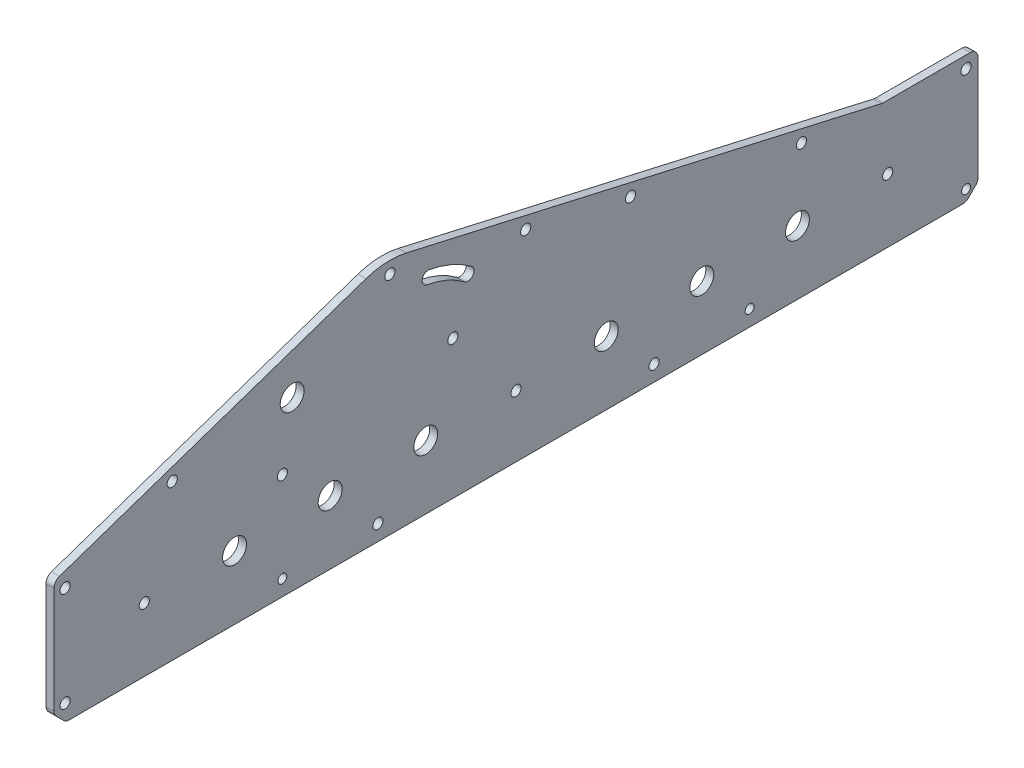
SolidWorks part; units mm, degrees
ref_plane "Front Plane" through (0, 0, 0) normal (0, 0, 1) x (1, 0, 0)
ref_plane "Top Plane" through (0, 0, 0) normal (0, 1, 0) x (1, 0, 0)
ref_plane "Right Plane" through (0, 0, 0) normal (1, 0, 0) x (0, 0, -1)
sketch "Sketch1" plane through (0, 0, 0) normal (1, 0, 0) x (0, 0, -1)
  line L0 (-184.15, 26.1937) -> (-59.8122, 68.5626)
  line L1 (-184.15, -24.6062) -> (184.15, -24.6062)
  line L2 (-184.15, -24.6062) -> (-184.15, 26.1937)
  line L3 (146.05, 26.1937) -> (184.15, 26.1937)
  line L4 (184.15, -24.6062) -> (184.15, 26.1937)
  line L9 (146.05, 26.1937) -> (-43.7083, 69.4049)
  arc A0 (-59.8122, 68.5626) -> (-43.7083, 69.4049) centre (-50.2741, 40.5715) cw
  arc A4 (-45.783, 38.8051) -> (-54.7652, 42.3379) centre (-50.2741, 40.5715) ccw construction
  arc A5 (-42.7051, 69.1579) -> (-57.8431, 69.1579) centre (-50.2741, 40.5715) ccw construction
  point P6 (0, -24.6062)
  dimension "D1" = 50.8
  dimension "D2" = 368.3
  dimension "D3" = 24.6062
  dimension "D5" = 38.1
extrude "Boss-Extrude1" add sketch "Sketch1" along normal blind 3.175
chamfer "Chamfer1" distance 4.7625 angle 45 2 edges at (1.5875, -24.6062, -184.15) (1.5875, -24.6062, 184.15)
fillet "Fillet1" radius 3.175 7 edges at (1.5875, -24.6062, -179.3875) (1.5875, -19.8437, -184.15) (1.5875, 26.1937, -184.15) (1.5875, -24.6062, 179.3875) (1.5875, -19.8437, 184.15) (1.5875, 26.1937, 184.15) (1.5875, 26.1937, -146.05)
sketch "Sketch4" plane through (3.175, 0, 0) normal (1, 0, 0) x (0, 0, -1)
  circle A0 centre (-137.0088, 37.226) radius 1.905 construction
  circle A2 centre (3.8736, 53.6853) radius 1.905 construction
  circle A3 centre (45.6663, 44.1684) radius 1.905 construction
  circle A4 centre (113.7728, 28.6594) radius 1.905 construction
  circle A5 centre (-25.1593, 30.6938) radius 2.032 construction
  circle A6 centre (-50.2741, 65.3805) radius 1.905 construction
  point P3 (0, 0)
  point P9 (55.0246, -18.3223)
  point P11 (-55.0246, -18.3223)
  point P13 (-179.705, 21.7487)
  point P15 (-179.705, -18.0026)
  point P17 (179.3875, 21.4312)
  point P19 (148.1579, 0.7938)
  point P21 (-148.1579, 0.7937)
  point P25 (-93.1246, 17.5943)
  point P28 (-137.0088, 37.226)
  point P32 (3.8736, 53.6853)
  point P34 (45.6663, 44.1684)
  point P36 (113.7728, 28.6594)
  point P54 (-25.1593, 30.6938)
  point P59 (-50.2741, 65.3805)
hole_wizard "#8 Clearance Hole1" positions "Sketch4" profile "Sketch5" hole size "#8" standard "ANSI Inch" end condition up to next
sketch "Sketch5" plane through (3.175, 0, 0) normal (0, 1, 0) x (0, 0, -1)
  line L0 (0, 0) -> (0, 3.175)
  line L1 (0, 3.175) -> (2.032, 3.175)
  line L2 (2.032, 3.175) -> (2.032, 0)
  line L5 (2.032, 0) -> (0, 0)
  line L11 (0, -6.35) -> (0, 107.95) construction
  dimension "Thru Hole Dia." = 4.064
  dimension "Thru Hole Depth" = 3.175
sketch "Sketch6" plane through (3.175, 0, 0) normal (1, 0, 0) x (0, 0, -1)
  point P0 (-93.1246, -18.3223)
  point P1 (93.1246, -18.3223)
  point P3 (179.3875, -20.1161)
hole_wizard "#8 Clearance Hole2" positions "Sketch6" profile "Sketch7" hole size "#8" standard "ANSI Inch" end condition up to next
sketch "Sketch7" plane through (3.175, -18.3223, 93.1246) normal (0, 1, 0) x (0, 0, -1)
  line L0 (0, 0) -> (0, 3.175)
  line L1 (0, 3.175) -> (1.778, 3.175)
  line L2 (1.778, 3.175) -> (1.778, 0)
  line L5 (1.778, 0) -> (0, 0)
  line L11 (0, -6.35) -> (0, 107.95) construction
  dimension "Thru Hole Dia." = 3.556
  dimension "Thru Hole Depth" = 3.175
sketch "Sketch8" plane through (3.175, 0, 0) normal (1, 0, 0) x (0, 0, -1)
  circle A0 centre (-89.211, 42.2593) radius 4.7625 construction
  point P0 (-112.1746, 0.7937)
  point P1 (-74.0746, 0.7937)
  point P3 (-35.9746, 0.7938)
  point P5 (35.9746, 0.7937)
  point P7 (74.0746, 0.7937)
  point P9 (112.1746, 0.7937)
  point P13 (-89.211, 42.2593)
hole_wizard "3/8 Clearance Hole1" positions "Sketch8" profile "Sketch9" hole size "3/8" standard "ANSI Inch" end condition up to next
sketch "Sketch9" plane through (3.175, 0.7937, 112.1746) normal (0, 1, 0) x (0, 0, -1)
  line L0 (0, 0) -> (0, 3.175)
  line L1 (0, 3.175) -> (4.7625, 3.175)
  line L2 (4.7625, 3.175) -> (4.7625, 0)
  line L5 (4.7625, 0) -> (0, 0)
  line L11 (0, -6.35) -> (0, 107.95) construction
  dimension "Thru Hole Dia." = 9.525
  dimension "Thru Hole Depth" = 3.175
sketch "Sketch10" plane through (3.175, 0, 0) normal (1, 0, 0) x (0, 0, -1)
  arc A0 (-34.5594, 59.0407) -> (-35.4169, 54.2915) centre (-34.9881, 56.6661) ccw construction
  arc A1 (-20.5473, 47.8719) -> (-35.4169, 54.2915) centre (-41.7582, 19.1724) ccw construction
  arc A2 (-20.5473, 47.8719) -> (-17.6789, 51.753) centre (-19.1131, 49.8125) ccw construction
  arc A3 (-17.6789, 51.753) -> (-34.5594, 59.0407) centre (-41.7582, 19.1724) ccw construction
  arc A4 (-34.5594, 59.0407) -> (-35.4169, 54.2915) centre (-34.9881, 56.6661) ccw
  arc A5 (-20.5473, 47.8719) -> (-35.4169, 54.2915) centre (-41.7582, 19.1724) ccw
  arc A6 (-20.5473, 47.8719) -> (-17.6789, 51.753) centre (-19.1131, 49.8125) ccw
  arc A7 (-17.6789, 51.753) -> (-34.5594, 59.0407) centre (-41.7582, 19.1724) ccw
extrude "Cut-Extrude1" cut sketch "Sketch10" against normal through all
